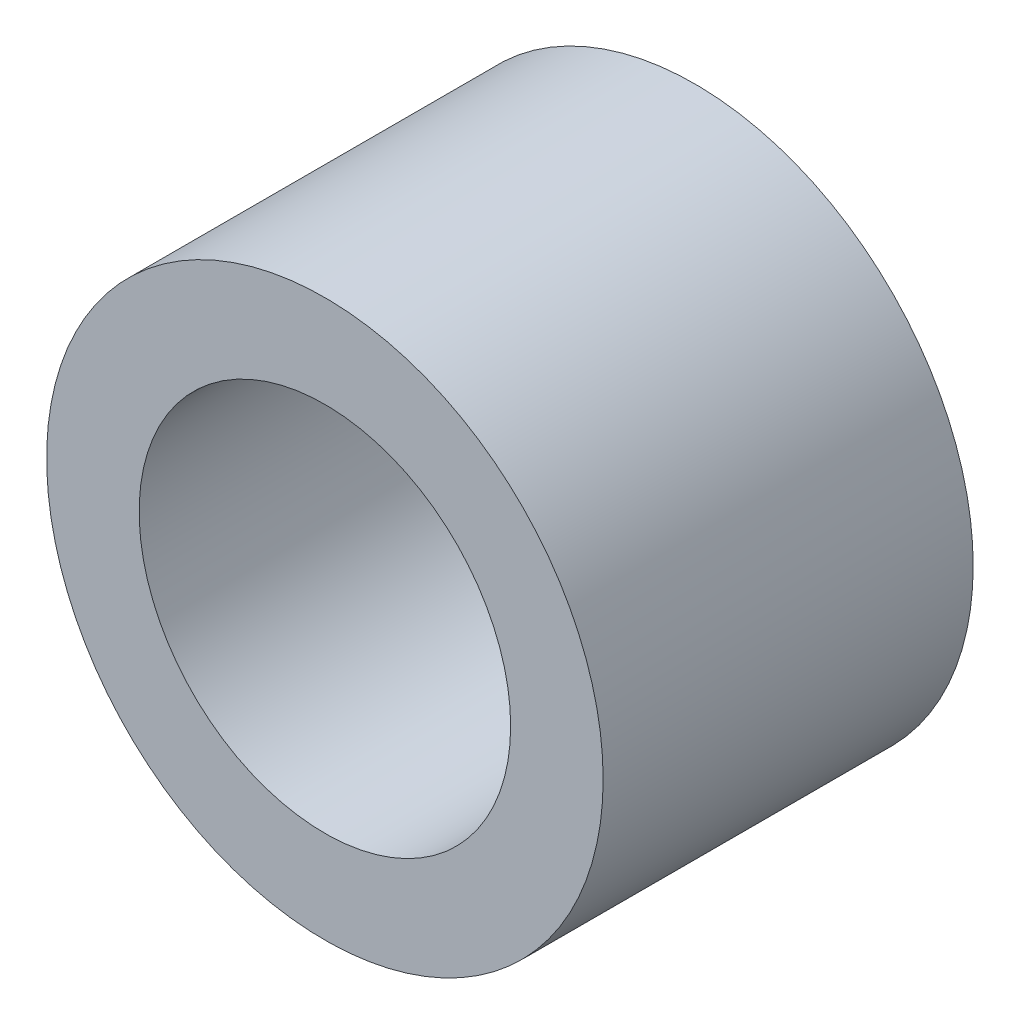
SolidWorks part; units mm, degrees
ref_plane "Front Plane" through (0, 0, 0) normal (0, 0, 1) x (1, 0, 0)
ref_plane "Top Plane" through (0, 0, 0) normal (0, 1, 0) x (1, 0, 0)
ref_plane "Right Plane" through (0, 0, 0) normal (1, 0, 0) x (0, 0, -1)
sketch "Sketch1" plane through (0, 0, 0) normal (0, 0, 1) x (1, 0, 0)
  circle A0 centre (0, 0) radius 4.7752
  circle A1 centre (0, 0) radius 3.1877
  dimension "OD" = 9.5504
  dimension "ID" = 6.3754
sketch "Sketch2" plane through (0, 0, 0) normal (1, 0, 0) x (0, 0, -1)
  line L2 (3.175, 0) -> (-3.175, 0) construction
  line L4 (-3.175, -4.7752) -> (-3.175, 4.7752) construction
  line L5 (-3.175, -3.1877) -> (3.175, -3.1877)
  line L6 (3.175, 3.1877) -> (-3.175, 3.1877)
  line L7 (3.175, -4.7752) -> (3.175, 4.7752) construction
  line L8 (-3.175, 4.7752) -> (3.175, 4.7752) construction
  line L9 (-3.175, -4.7752) -> (3.175, -4.7752) construction
  line L10 (0, 4.7752) -> (0, -4.7752) construction
  line L11 (0, 3.1877) -> (0, -3.1877) construction
  point P4 (0, -3.1877)
  point P7 (0, 3.1877)
  point P8 (0, 0)
  point P12 (-3.175, 0)
  point P15 (3.175, 0)
  point P16 (0, -4.7752)
  point P17 (0, 4.7752)
  dimension "Length" = 6.35
sketch "Sketch5" plane through (0, 0, 0) normal (0, 0, 1) x (1, 0, 0)
  circle A1 centre (0, 0) radius 3.1877
  circle A2 centre (0, 0) radius 3.1877
  circle A3 centre (0, 0) radius 4.7752
  circle A4 centre (0, 0) radius 4.7752
  dimension "D1" = 0
  dimension "D2" = 0
extrude "Boss-Extrude1" add sketch "Sketch5" along normal up to vertex (3.175 mm away) and the other way up to vertex (3.175 mm away) up to point (0, 0, 3.175) other way up to point (0, 0, -3.175)
sketch "Sketch4" plane through (0, 0, 3.175) normal (0, 0, 1) x (1, 0, 0)
  line L0 (0, 0) -> (-2.254, 2.254)
  line L2 (0, -4.7752) -> (0, 4.7752) construction
  circle A1 centre (0, 0) radius 3.1877 construction
  dimension "D1" = 45
equation "\"D1\"= \"Length@Sketch2\""
